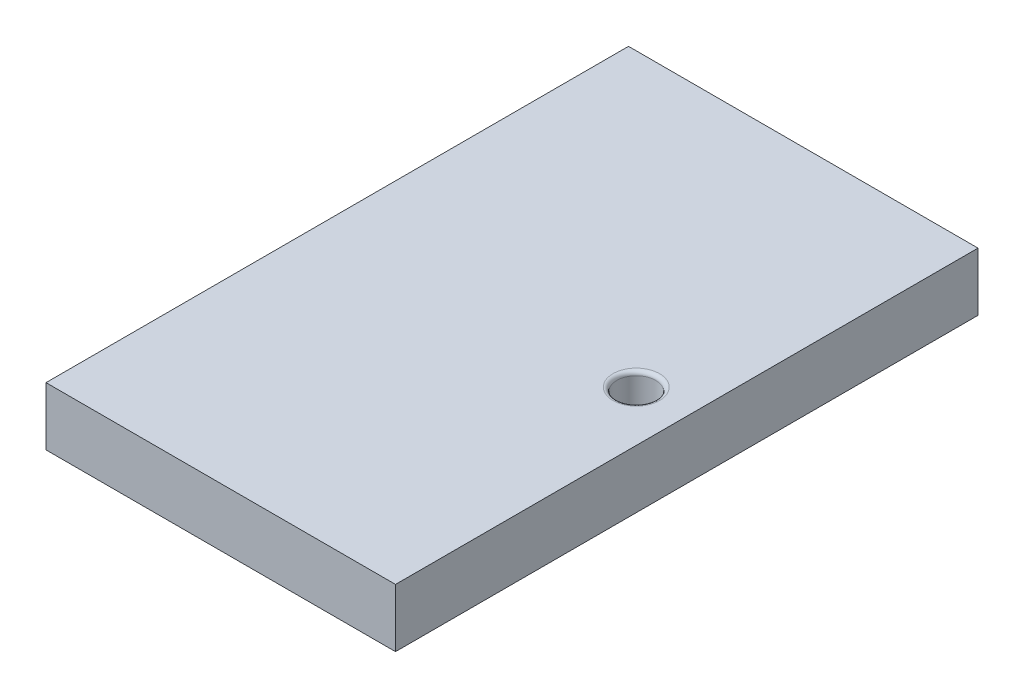
SolidWorks part; units mm, degrees
ref_plane "前视基准面" through (0, 0, 0) normal (0, 0, 1) x (1, 0, 0)
ref_plane "上视基准面" through (0, 0, 0) normal (0, 1, 0) x (1, 0, 0)
ref_plane "右视基准面" through (0, 0, 0) normal (1, 0, 0) x (0, 0, -1)
other "Configuration Table"
sketch "草图1" plane through (0, 0, 0) normal (0, 1, 0) x (1, 0, 0)
  line L0 (18, 15) -> (0, 15) construction
  line L1 (0, 0) -> (18, 0)
  line L2 (0, 0) -> (0, 30)
  line L3 (0, 30) -> (18, 30)
  line L4 (18, 0) -> (18, 30)
  circle A0 centre (15.4, 15) radius 1
  dimension "D3" = 2
  dimension "D1" = 30
  dimension "D2" = 18
  dimension "D4" = 2.6
extrude "凸台-拉伸1" add sketch "草图1" along normal blind 3 contours L0 L4 L3 L2 A0 | L4 L0 A0 L2 L1 region at (8.9625, 0, -7.4586) region at (8.9625, 0, -22.5414)
fillet "圆角1" radius 0.2 1 edges at (15.4, 3, -14)
